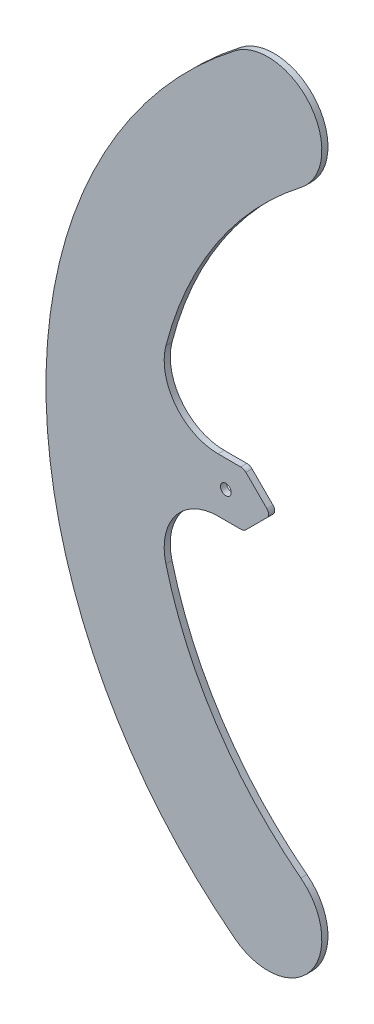
SolidWorks part; units mm, degrees
ref_plane "Front Plane" through (0, 0, 0) normal (0, 0, 1) x (1, 0, 0)
ref_plane "Top Plane" through (0, 0, 0) normal (0, 1, 0) x (1, 0, 0)
ref_plane "Right Plane" through (0, 0, 0) normal (1, 0, 0) x (0, 0, -1)
sketch "Sketch1" plane through (0, 0, 0) normal (0, 0, 1) x (1, 0, 0)
  line L0 (-32.8019, 0) -> (18.2589, 0) construction
  line L1 (70.5, 105) -> (70.5, 135) construction
  line L2 (205.5, -110) -> (-64.5, -110)
  line L3 (205.5, -110) -> (205.5, 110)
  line L4 (205.5, 110) -> (-64.5, 110)
  line L5 (-19.5, 6) -> (-19.5, -6)
  line L6 (-18, -7.5) -> (-9.5, -7.5)
  line L7 (-9.5, -7.5) -> (-3.0607, -1.0607)
  line L8 (-3.0607, 1.0607) -> (-9.5, 7.5)
  line L9 (-9.5, 7.5) -> (-18, 7.5)
  line L10 (-19.5, 6) -> (-19.5, -6)
  line L11 (-18, -7.5) -> (-9.5, -7.5)
  line L12 (-9.5, -7.5) -> (-3.0607, -1.0607)
  line L13 (-3.0607, 1.0607) -> (-9.5, 7.5)
  line L14 (-9.5, 7.5) -> (-18, 7.5)
  line L15 (-64.5, -110) -> (-64.5, 110)
  line L16 (205.5, -110) -> (-64.5, 110) construction
  line L17 (205.5, 110) -> (-64.5, -110) construction
  line L18 (-18, 7.5) -> (-34.2318, 7.5)
  line L19 (-18, -7.5) -> (-34.2318, -7.5)
  circle A0 centre (-14.5, 0) radius 1.5 construction
  arc A2 (-19.5, -6) -> (-18, -7.5) centre (-18, -6) ccw
  arc A3 (-18, 7.5) -> (-19.5, 6) centre (-18, 6) ccw
  arc A4 (-19.5, -6) -> (-18, -7.5) centre (-18, -6) ccw
  arc A5 (-18, 7.5) -> (-19.5, 6) centre (-18, 6) ccw
  circle A6 centre (-14.5, 0) radius 1.5
  circle A7 centre (-14.5, 0) radius 1.5
  circle A8 centre (70.5, 0) radius 135
  circle A9 centre (70.5, 0) radius 105
  circle A11 centre (-2.8144, 95) radius 15
  circle A12 centre (-2.8144, -95) radius 15
  arc A32 (-3.0607, -1.0607) -> (-3.0607, 1.0607) centre (-4.1213, 0) ccw
  arc A33 (-3.0607, -1.0607) -> (-3.0607, 1.0607) centre (-4.1213, 0) ccw
  point P19 (-64.5, 0)
  point P27 (70.5, 110)
  dimension "D3" = 270
  dimension "D5" = 30
  dimension "D2" = 55
  dimension "D4" = 220
  dimension "D1" = 0
extrude "Boss-Extrude1" add sketch "Sketch1" along normal blind 1.7 contours A11 | A8 A12 A9 A11 | A12 | L18 A9 L19 A4 L10 A5 | L14 A5 L10 A4 L11 L12 L13 A6 region at (-2.8144, -95, 0) region at (-37.1858, 0, 0) region at (-2.8144, 95, 0) region at (-26.922, 0, 0) region at (-12.373, 0, 0)
fillet "Fillet1" radius 15 2 edges at (-34.2318, -7.5, 0.85) (-34.2318, 7.5, 0.85)
fillet "Fillet2" radius 2 2 edges at (-9.5, -7.5, 0.85) (-9.5, 7.5, 0.85)
